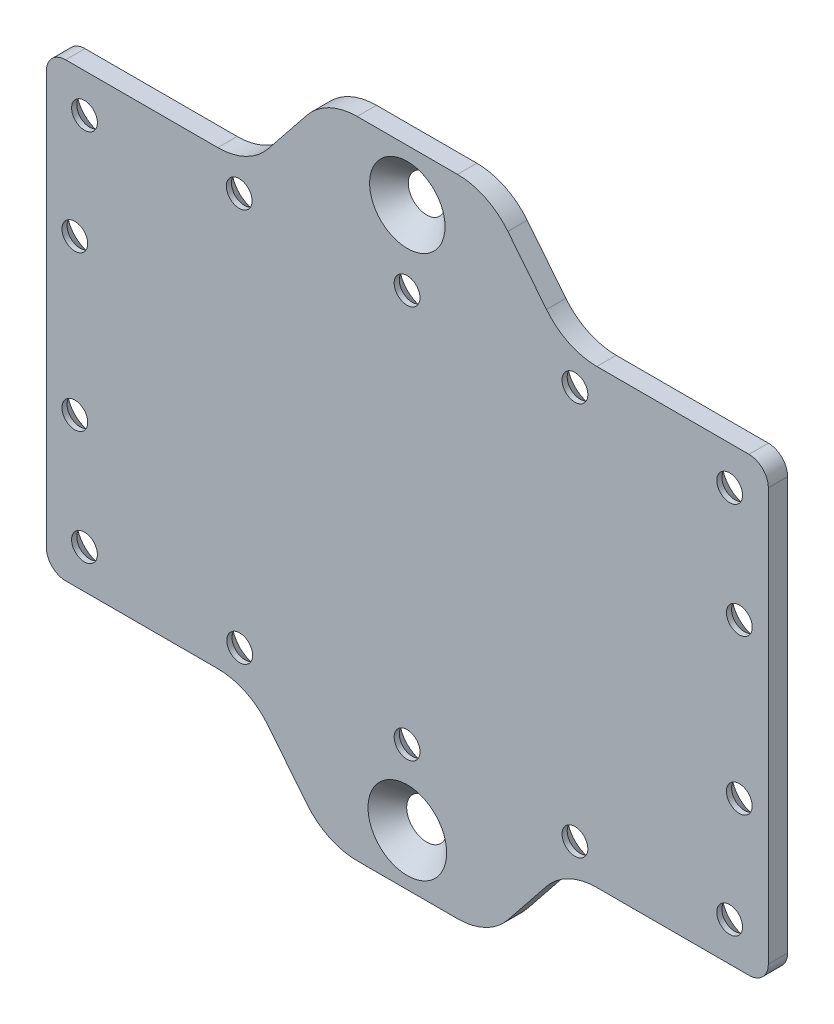
SolidWorks part; units mm, degrees
material "6063-O"
ref_plane "Front Plane" through (0, 0, 0) normal (0, 0, 1) x (1, 0, 0)
ref_plane "Top Plane" through (0, 0, 0) normal (0, 1, 0) x (1, 0, 0)
ref_plane "Right Plane" through (0, 0, 0) normal (1, 0, 0) x (0, 0, -1)
sketch "Sketch1" plane through (0, 0, 0) normal (0, 0, 1) x (1, 0, 0)
  line L1 (-42.6192, 55.8813) -> (63.3808, 55.8813)
  line L2 (-45.6192, 52.8813) -> (-45.6192, -41.1187)
  line L3 (-42.6192, -44.1187) -> (63.3808, -44.1187)
  line L4 (66.3808, 52.8813) -> (66.3808, -41.1187)
  arc A0 (-45.6192, -41.1187) -> (-42.6192, -44.1187) centre (-42.6192, -41.1187) ccw
  arc A1 (63.3808, -44.1187) -> (66.3808, -41.1187) centre (63.3808, -41.1187) ccw
  arc A2 (66.3808, 52.8813) -> (63.3808, 55.8813) centre (63.3808, 52.8813) ccw
  arc A3 (-45.6192, 52.8813) -> (-42.6192, 55.8813) centre (-42.6192, 52.8813) cw
  point P6 (-45.6192, -44.1187)
  point P11 (66.3808, 55.8813)
  point P14 (-45.6192, 55.8813)
  dimension "D3" = 3
  dimension "D1" = 112
  dimension "D2" = 100
extrude "Boss-Extrude1" add sketch "Sketch1" along normal blind 3
sketch "Sketch3" plane through (0, 0, 3) normal (0, 0, 1) x (1, 0, 0)
  line L2 (63.3808, 55.8813) -> (-42.6192, 55.8813) construction
  line L3 (7.2808, 55.8813) -> (13.4808, 55.8813)
  line L5 (-42.6192, -44.1187) -> (63.3808, -44.1187) construction
  line L6 (10.3808, 24.2476) -> (10.3808, -7.2931) construction
  line L8 (39.7786, 40.8813) -> (66.3808, 40.8813)
  line L9 (66.3808, -41.1187) -> (66.3808, 52.8813) construction
  line L10 (22.9721, 55.8813) -> (31.9699, 44.6343)
  line L11 (22.9721, 55.8813) -> (13.4808, 55.8813)
  line L13 (-19.0169, 40.8813) -> (-45.6192, 40.8813)
  line L14 (-2.2104, 55.8813) -> (-11.2083, 44.6343)
  line L15 (-57.8903, 5.8813) -> (91.1459, 5.8813) construction
  line L16 (39.7786, -29.1187) -> (66.3808, -29.1187)
  line L17 (22.9721, -44.1187) -> (31.9699, -32.8716)
  line L18 (-2.2104, -44.1187) -> (-11.2083, -32.8716)
  line L19 (-19.0169, -29.1187) -> (-45.6192, -29.1187)
  line L20 (-45.6192, 40.8813) -> (-45.6192, 63.9158)
  line L21 (-45.6192, 63.9158) -> (-2.2104, 63.9158)
  line L22 (-2.2104, 63.9158) -> (-2.2104, 55.8813)
  line L23 (22.9721, 63.9158) -> (22.9721, 55.8813)
  line L24 (66.3808, 40.8813) -> (66.3808, 63.9158)
  line L25 (66.3808, 63.9158) -> (22.9721, 63.9158)
  line L26 (66.3808, -29.1187) -> (66.3808, -52.1531)
  line L27 (22.9721, -52.1531) -> (22.9721, -44.1187)
  line L28 (66.3808, -52.1531) -> (22.9721, -52.1531)
  line L29 (-45.6192, -29.1187) -> (-45.6192, -52.1531)
  line L30 (-2.2104, -52.1531) -> (-2.2104, -44.1187)
  line L31 (-45.6192, -52.1531) -> (-2.2104, -52.1531)
  circle A1 centre (10.3808, -36.1187) radius 3
  arc A2 (39.7786, 40.8813) -> (31.9699, 44.6343) centre (39.7786, 50.8813) cw
  arc A3 (-19.0169, 40.8813) -> (-11.2083, 44.6343) centre (-19.0169, 50.8813) ccw
  arc A4 (39.7786, -29.1187) -> (31.9699, -32.8716) centre (39.7786, -39.1187) ccw
  arc A5 (-19.0169, -29.1187) -> (-11.2083, -32.8716) centre (-19.0169, -39.1187) cw
  circle A6 centre (10.3808, 47.8813) radius 3
  arc M1 (-45.6192, -41.1187) -> (-42.6192, -44.1187) centre (-42.6192, -41.1187) ccw
  line M2 (-42.6192, -44.1187) -> (63.3808, -44.1187)
  arc M3 (63.3808, -44.1187) -> (66.3808, -41.1187) centre (63.3808, -41.1187) ccw
  line M4 (66.3808, -41.1187) -> (66.3808, 52.8813)
  arc M5 (66.3808, 52.8813) -> (63.3808, 55.8813) centre (63.3808, 52.8813) ccw
  line M6 (63.3808, 55.8813) -> (-42.6192, 55.8813)
  arc M7 (-42.6192, 55.8813) -> (-45.6192, 52.8813) centre (-42.6192, 52.8813) ccw
  line M8 (-45.6192, 52.8813) -> (-45.6192, -41.1187)
  dimension "D4" = 8
  dimension "D5" = 10
  dimension "D1" = 6
  dimension "D6" = 50
  dimension "D7" = 35
extrude "Cut-Extrude1" cut sketch "Sketch3" against normal blind 10 contours L22 L21 L20 M7 M6 | L13 A3 L14 M6 M7 M8 | L24 L25 L23 M6 M5 | A2 L8 L10 M4 M5 M6 | L16 A4 L17 M2 M3 M4 | L28 L26 L27 M3 M2 | A5 L19 L18 M8 M1 M2 | L29 L31 L30 M2 M1 | A1 | A1 region at (-24.0306, 59.8727, 3) region at (-26.7626, 48.8017, 3) region at (47.5243, 48.8017, 3) region at (44.7923, 59.8727, 3) region at (-26.7626, -37.0391, 3) region at (47.5243, -37.0391, 3) region at (-24.0306, -48.1101, 3) region at (44.7923, -48.1101, 3) region at (10.3808, -36.1187, 3)
fillet "Fillet1" radius 10 4 edges at (-2.2104, 55.8813, 1.5) (22.9721, 55.8813, 1.5) (-2.2104, -44.1187, 1.5) (22.9721, -44.1187, 1.5)
fillet "Fillet2" radius 3 4 edges at (-45.6192, 40.8813, 1.5) (-45.6192, -29.1187, 1.5) (66.3808, 40.8813, 1.5) (66.3808, -29.1187, 1.5)
sketch "Sketch5" plane through (0, 0, 3) normal (0, 0, 1) x (1, 0, 0)
  circle A0 centre (-39.7, 34.8813) radius 2
  circle A1 centre (-15.7, 36.3813) radius 2
  circle A2 centre (10.3404, 36.3813) radius 2
  circle A3 centre (36.3808, 36.3813) radius 2
  circle A4 centre (60.3808, 34.8813) radius 2
  circle A5 centre (61.8808, 17.8813) radius 2
  circle A6 centre (61.8808, -6.1187) radius 2
  circle A7 centre (60.3808, -23.1187) radius 2
  circle A8 centre (36.3808, -24.6187) radius 2
  circle A9 centre (10.3404, -24.6187) radius 2
  circle A10 centre (-15.6192, -24.6187) radius 2
  circle A11 centre (-39.7, -23.1187) radius 2
  circle A12 centre (-41.2, -6.1187) radius 2
  circle A13 centre (-41.2, 17.8813) radius 2
  dimension "D1" = 4
extrude "Cut-Extrude3" cut sketch "Sketch5" against normal blind 5 and the other way blind 5
chamfer "Chamfer2" distance 2.2 angle 45 14 edges at (-39.2, 17.8813, 0) (-37.7, 34.8813, 0) (-13.7, 36.3813, 0) (12.3404, 36.3813, 0) (38.3808, 36.3813, 0) (62.3808, 34.8813, 0) (63.8808, 17.8813, 0) (63.8808, -6.1187, 0) (62.3808, -23.1187, 0) (38.3808, -24.6187, 0) (12.3404, -24.6187, 0) (-13.6192, -24.6187, 0) (-39.2, -6.1187, 0) (-37.7, -23.1187, 0)
sketch "Sketch6" plane through (0, 0, 3) normal (0, 0, 1) x (1, 0, 0)
  line L0 (18.1659, 55.8813) -> (2.5958, 55.8813) construction
  line L1 (-45.6192, 37.8813) -> (-45.6192, -26.1187) construction
  circle A0 centre (10.3808, 47.8813) radius 2.7497
  point P4 (10.3808, 55.8813)
  dimension "D1" = 8
  dimension "D2" = 56
extrude "Cut-Extrude4" cut sketch "Sketch6" against normal blind 10
chamfer "Chamfer3" distance 3.1 angle 45 2 edges at (13.3808, -36.1187, 3) (13.1306, 47.8813, 3)
